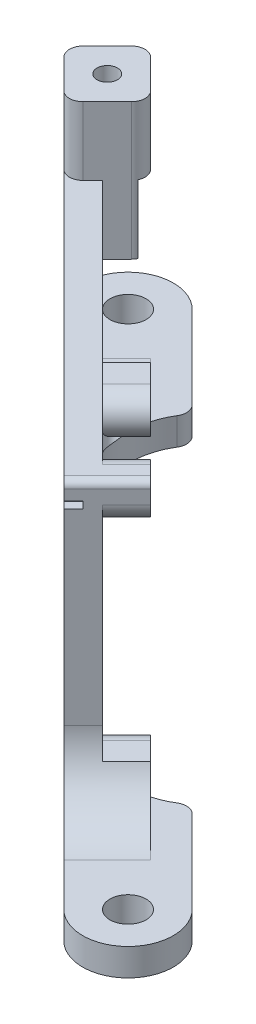
SolidWorks part; units mm, degrees
ref_plane "前视基准面" through (0, 0, 0) normal (0, 0, 1) x (1, 0, 0)
ref_plane "上视基准面" through (0, 0, 0) normal (0, 1, 0) x (1, 0, 0)
ref_plane "右视基准面" through (0, 0, 0) normal (1, 0, 0) x (0, 0, -1)
sketch "草图1" plane through (0, 0, 0) normal (0, 1, 0) x (1, 0, 0)
  line L0 (38.1, -38.1) -> (-38.1, 38.1)
  line L1 (38.1, -38.1) -> (-38.1, 38.1) construction
  line L2 (33.3977, -42.8023) -> (-42.8023, 33.3977)
  line L3 (42.8023, -33.3977) -> (-33.3977, 42.8023)
  circle A0 centre (38.1, -38.1) radius 2.65
  circle A1 centre (-38.1, 38.1) radius 2.65
  arc A2 (33.3977, -42.8023) -> (42.8023, -33.3977) centre (38.1, -38.1) ccw
  arc A3 (-33.3977, 42.8023) -> (-42.8023, 33.3977) centre (-38.1, 38.1) ccw
  point P4 (0, 0)
  point P7 (0, 0)
  dimension "D3" = 5.3
  dimension "D4" = 5.3
  dimension "D5" = 4
  dimension "D1" = 76.2
  dimension "D2" = 76.2
extrude "凸台-拉伸1" add sketch "草图1" along normal blind 4 contours L3 A3 L2 A2 A1 A0 region at (-3.8073, 0, 3.8073)
sketch "草图2" plane through (-4.7023, 0, 4.7023) normal (-0.7071, 0, 0.7071) x (0.7071, 0, 0.7071)
  line L0 (53.8815, 4) -> (-53.8815, 4) construction
  line L1 (35, 45) -> (-35, 45)
  line L2 (35, 45) -> (35, 4)
  line L3 (35, 4) -> (-35, 4)
  line L4 (-35, 45) -> (-35, 4)
  line L5 (35, 45) -> (-35, 4) construction
  line L6 (35, 4) -> (-35, 45) construction
  point P0 (0, 24.5)
  dimension "D1" = 70
  dimension "D2" = 0
  dimension "D3" = 41
extrude "凸台-拉伸2" add sketch "草图2" against normal blind 4
sketch "草图3" plane through (0, 4, 0) normal (0, 1, 0) x (1, 0, 0)
  line L0 (-26.6226, 22.8749) -> (-15.8803, 33.6172)
  line L1 (-15.8803, 33.6172) -> (33.6172, -15.8803)
  line L2 (22.8749, -26.6226) -> (33.6172, -15.8803)
  line M5 (-26.6226, 22.8749) -> (22.8749, -26.6226)
  line M9 (42.8023, -33.3977) -> (-33.3977, 42.8023)
  dimension "D1" = 270
extrude "切除-拉伸1" cut sketch "草图3" against normal blind 4 and the other way through all contours L2 L0 M5 M9 region at (1.4142, 4, -1.4142)
fillet "圆角1" radius 10 2 edges at (22.8749, 2, 26.6226) (-26.6226, 2, -22.8749)
fillet "圆角2" radius 10 2 edges at (21.4607, 4, 28.0368) (-28.0368, 4, -21.4607)
fillet "圆角3" radius 2 2 edges at (22.8836, 4, 26.6312) (-26.6312, 4, -22.8836)
fillet "圆角4" radius 1 2 edges at (21.4607, 45, 28.0368) (-28.0368, 45, -21.4607)
sketch "草图4" plane through (-1.8738, 0, 1.8738) normal (0.7071, 0, -0.7071) x (-0.7071, 0, -0.7071)
  line L0 (0, 45) -> (0, 0)
  line L1 (-34, 45) -> (34, 45) construction
  line L3 (32, 7) -> (-32, 7)
  line L4 (32, 7) -> (32, 42)
  line L5 (32, 42) -> (-32, 42)
  line L6 (-32, 7) -> (-32, 42)
  line L7 (32, 7) -> (-32, 42) construction
  line L8 (32, 42) -> (-32, 7) construction
  circle A0 centre (-32, 42) radius 1.65
  circle A1 centre (-32, 7) radius 1.65
  circle A2 centre (32, 42) radius 1.65
  circle A3 centre (32, 7) radius 1.65
  point P5 (0, 24.5)
  line M7 (-39, 6) -> (-25.0245, 6)
  line M11 (25.0245, 6) -> (39, 6)
  dimension "D4" = 3.3
  dimension "D5" = 3.3
  dimension "D6" = 3.3
  dimension "D7" = 3.3
  dimension "D1" = 20.5
  dimension "D2" = 35
  dimension "D3" = 64
extrude "切除-拉伸2" cut sketch "草图4" against normal mid plane 14 contours L6 A0 L5 | L5 A0 L6 | L4 A2 L5 | L5 A2 L4 | L3 A3 L4 M11 | L4 A3 L3 | L6 A1 L3 M7 | L3 A1 L6 | A3 M11 | A1 M7 region at (-24.6663, 42.2334, -20.9186) region at (-24.0061, 41.2997, -20.2584) region at (20.2584, 41.2997, 24.0061) region at (20.9186, 42.2334, 24.6663) region at (-24.0061, 7.7003, -20.2584) region at (-24.704, 7.0019, -20.9563) region at (20.9563, 7.0019, 24.704) region at (20.2584, 7.7003, 24.0061) region at (-24.5012, 5.735, -20.7536) region at (20.7536, 5.735, 24.5012)
sketch "草图5" plane through (-1.8738, 0, 1.8738) normal (0.7071, 0, -0.7071) x (-0.7071, 0, -0.7071)
  line L1 (32, 4) -> (46.1458, 4)
  line L2 (-32, 42) -> (-35, 42)
  line L3 (-32, 42) -> (-32, 45.9419)
  line L4 (-32, 45.9419) -> (-35, 45.9419)
  line L5 (-35, 42) -> (-35, 45.9419)
  line L6 (32, 42) -> (35, 42)
  line L7 (32, 42) -> (32, 47.5251)
  line L8 (32, 47.5251) -> (35, 47.5251)
  line L9 (35, 42) -> (35, 47.5251)
  line L10 (-32, 7) -> (-39, 7)
  line L11 (-30.6876, 6) -> (-25.0245, 6)
  line L12 (-25.0245, 6) -> (-25.0245, 0)
  line L13 (-25.0245, 0) -> (25.0245, 0)
  line L14 (25.0245, 0) -> (25.0245, 6)
  line L15 (25.0245, 6) -> (30.6876, 6)
  line L16 (33.3124, 6) -> (39, 6)
  line L17 (35, 14) -> (35, 44)
  line L18 (34, 45) -> (-34, 45)
  line L19 (-35, 44) -> (-35, 14)
  line L20 (-39, 6) -> (-33.3124, 6)
  line L21 (-30.6876, 6) -> (-25.0245, 6)
  line L22 (-25.0245, 6) -> (-25.0245, 0)
  line L23 (-25.0245, 0) -> (25.0245, 0)
  line L24 (25.0245, 0) -> (25.0245, 6)
  line L25 (25.0245, 6) -> (30.6876, 6)
  line L26 (33.3124, 6) -> (39, 6)
  line L27 (35, 14) -> (35, 44)
  line L28 (34, 45) -> (-34, 45)
  line L29 (-35, 44) -> (-35, 14)
  line L30 (-39, 6) -> (-33.3124, 6)
  line L31 (-32, 7) -> (-32, 10)
  line L32 (-32, 10) -> (-39, 10)
  line L33 (-39, 7) -> (-39, 10)
  line L34 (32, 7) -> (39.2652, 7)
  line L35 (32, 7) -> (32, 10)
  line L36 (32, 10) -> (39.2652, 10)
  line L37 (39.2652, 7) -> (39.2652, 10)
  line L38 (35, 4) -> (53.8815, 4) construction
  line L39 (46.1458, 4) -> (39.2652, 7)
  line L40 (-32, 4) -> (-46.5387, 4)
  line L41 (-53.8815, 4) -> (-35, 4) construction
  line L42 (-46.5387, 4) -> (-39, 7)
  circle A0 centre (-32, 42) radius 3
  circle A1 centre (-32, 7) radius 3
  circle A2 centre (32, 7) radius 3
  circle A3 centre (32, 42) radius 3
  circle A4 centre (-32, 7) radius 1.65
  circle A5 centre (32, 7) radius 1.65
  arc A6 (39, 6) -> (45, 4) centre (45, 14) ccw construction
  arc A7 (-30.6876, 6) -> (-33.3124, 6) centre (-32, 7) ccw
  arc A8 (33.3124, 6) -> (30.6876, 6) centre (32, 7) ccw
  arc A9 (35, 14) -> (39, 6) centre (45, 14) ccw
  arc A10 (35, 44) -> (34, 45) centre (34, 44) ccw
  arc A11 (-34, 45) -> (-35, 44) centre (-34, 44) ccw
  arc A12 (-39, 6) -> (-35, 14) centre (-45, 14) ccw
  arc A13 (-30.6876, 6) -> (-33.3124, 6) centre (-32, 7) ccw
  arc A14 (33.3124, 6) -> (30.6876, 6) centre (32, 7) ccw
  arc A15 (35, 14) -> (39, 6) centre (45, 14) ccw
  arc A16 (35, 44) -> (34, 45) centre (34, 44) ccw
  arc A17 (-34, 45) -> (-35, 44) centre (-34, 44) ccw
  arc A18 (-39, 6) -> (-35, 14) centre (-45, 14) ccw
  arc A19 (-45, 4) -> (-39, 6) centre (-45, 14) ccw construction
  arc A20 (39, 6) -> (45, 4) centre (45, 14) ccw
  arc A21 (-45, 4) -> (-39, 6) centre (-45, 14) ccw
  arc M1 (-33.3124, 6) -> (-30.6876, 6) centre (-32, 7) cw
  line M2 (-30.6876, 6) -> (-25.0245, 6)
  arc M7 (30.6876, 6) -> (33.3124, 6) centre (32, 7) cw
  line M8 (33.3124, 6) -> (39, 6)
  arc M9 (39, 6) -> (35, 14) centre (45, 14) cw
  line M10 (35, 14) -> (35, 44)
  arc M11 (35, 44) -> (34, 45) centre (34, 44) ccw
  line M12 (34, 45) -> (-34, 45)
  arc M13 (-34, 45) -> (-35, 44) centre (-34, 44) ccw
  line M14 (-35, 44) -> (-35, 14)
  arc M15 (-35, 14) -> (-39, 6) centre (-45, 14) cw
  line M16 (-39, 6) -> (-33.3124, 6)
  circle M17 centre (32, 42) radius 1.65
  circle M18 centre (-32, 42) radius 1.65
  dimension "D1" = 6
  dimension "D3" = 6
  dimension "D4" = 6
  dimension "D5" = 3
  dimension "D6" = 3
  dimension "D2" = 0
extrude "凸台-拉伸3" add sketch "草图5" along normal blind 5 contours L35 A2 L25 M7 | L34 A2 L35 M7 | A2 L34 L36 M9 | A2 L26 L34 M9 | A20 L26 A2 L1 | A5 L25 A2 M8 | A2 L34 M8 M7 | A1 L10 M15 M16 | A21 L40 A1 M16 | A4 L30 A1 M2 | A1 L31 M2 M1 | L31 A1 L10 M1 | A1 L32 L10 M15 | L10 A1 L30 M1 | L2 A0 L3 M18 | L3 A0 L2 M18 | A0 M12 M13 M14 | L6 A3 L7 M17 | L7 A3 L6 M17 | A3 M10 M11 M12 region at (-28.4613, 4.8333, -24.7136) region at (-24.5012, 5.0765, -20.7536) region at (-23.3128, 8.0723, -19.5651) region at (-27.8155, 6.4684, -24.0678) region at (-26.0855, 6.4906, -22.3378) region at (-25.5773, 8.5217, -21.8296) region at (-26.9843, 8.5141, -23.2367) region at (-23.0437, 39.9387, -19.296) region at (-26.1092, 44.2741, -22.3616) region at (-25.5773, 43.5217, -21.8296) region at (20.7536, 5.0765, 24.5012) region at (19.5651, 8.0723, 23.3128) region at (24.7136, 4.8333, 28.4613) region at (19.296, 44.0613, 23.0437) region at (22.3616, 44.2741, 26.1092) region at (21.8296, 43.5217, 25.5773) region at (22.3378, 6.4906, 26.0855) region at (24.0678, 6.4684, 27.8155) region at (23.2367, 8.5141, 26.9843) region at (21.8296, 8.5217, 25.5773)
sketch "草图6" plane through (-4.7023, 0, 4.7023) normal (-0.7071, 0, 0.7071) x (0.7071, 0, 0.7071)
  line L1 (-28.7091, 42) -> (-30.3546, 44.85)
  line L2 (-30.3546, 44.85) -> (-33.6454, 44.85)
  line L3 (-33.6454, 44.85) -> (-35.2909, 42)
  line L4 (-35.2909, 42) -> (-33.6454, 39.15)
  line L5 (-33.6454, 39.15) -> (-30.3546, 39.15)
  line L6 (-30.3546, 39.15) -> (-28.7091, 42)
  line L7 (35.2909, 42) -> (33.6454, 44.85)
  line L8 (33.6454, 44.85) -> (30.3546, 44.85)
  line L9 (30.3546, 44.85) -> (28.7091, 42)
  line L10 (28.7091, 42) -> (30.3546, 39.15)
  line L11 (30.3546, 39.15) -> (33.6454, 39.15)
  line L12 (33.6454, 39.15) -> (35.2909, 42)
  line L13 (35.2909, 7) -> (33.6454, 9.85)
  line L14 (33.6454, 9.85) -> (30.3546, 9.85)
  line L15 (30.3546, 9.85) -> (28.7091, 7)
  line L16 (28.7091, 7) -> (30.3546, 4.15)
  line L17 (30.3546, 4.15) -> (33.6454, 4.15)
  line L18 (33.6454, 4.15) -> (35.2909, 7)
  line L19 (-28.7091, 7) -> (-30.3546, 9.85)
  line L20 (-30.3546, 9.85) -> (-33.6454, 9.85)
  line L21 (-33.6454, 9.85) -> (-35.2909, 7)
  line L22 (-35.2909, 7) -> (-33.6454, 4.15)
  line L23 (-33.6454, 4.15) -> (-30.3546, 4.15)
  line L24 (-30.3546, 4.15) -> (-28.7091, 7)
  circle A0 centre (-32, 42) radius 2.85 construction
  circle A1 centre (32, 42) radius 2.85 construction
  circle A2 centre (32, 7) radius 2.85 construction
  circle A3 centre (-32, 7) radius 2.85 construction
  dimension "D1" = 5.7
  dimension "D2" = 5.7
  dimension "D3" = 5.7
  dimension "D4" = 5.7
extrude "切除-拉伸3" cut sketch "草图6" against normal blind 2
fillet "圆角5" radius 2 2 edges at (-20.0465, 2, -29.451) (29.451, 2, 20.0465)
sketch "草图7" plane through (0, 0, 0) normal (0, 1, 0) x (1, 0, 0)
  circle A0 centre (14.4684, -760.0717) radius 5
  circle A1 centre (-14.7658, -793.7018) radius 5
  dimension "D1" = 10
  dimension "D2" = 10
sketch "草图8" plane through (0, 0, 0) normal (0, 1, 0) x (1, 0, 0)
  circle A0 centre (14.4684, -23.7283) radius 5
  circle A1 centre (-14.7658, 9.9018) radius 5
  dimension "D1" = 10
  dimension "D2" = 10
extrude "切除-拉伸5" cut sketch "草图8" along normal blind 5
sketch "草图9" plane through (0, 45, 0) normal (0, 1, 0) x (1, 0, 0)
  line L0 (-18.8444, 15.0967) -> (-15.3089, 18.6323)
  line L1 (20.7536, -24.5012) -> (-24.5012, 20.7536) construction
  line L2 (-18.8444, 15.0967) -> (-24.5012, 20.7536)
  line L3 (-24.5012, 20.7536) -> (-20.9657, 24.2891)
  line L4 (-20.9657, 24.2891) -> (-15.3089, 18.6323)
  line L5 (-26.6226, 22.8749) -> (-29.451, 20.0465) construction
  line L6 (-18.8444, 22.1678) -> (-22.3799, 18.6323)
  line L7 (-18.8444, 22.1678) -> (-11.7733, 15.0967)
  line L8 (-22.3799, 18.6323) -> (-15.3089, 11.5612)
  line L9 (-11.7733, 15.0967) -> (-15.3089, 11.5612)
  line L10 (-18.8444, 22.1678) -> (-15.3089, 11.5612) construction
  line L11 (-22.3799, 18.6323) -> (-11.7733, 15.0967) construction
  line L12 (19.3394, -28.7439) -> (-28.7439, 19.3394) construction
  circle A1 centre (-18.4908, 15.4503) radius 1.5
  line M7 (20.7536, -24.5012) -> (-24.5012, 20.7536)
  line M8 (-24.5012, 20.7536) -> (-20.9657, 24.2891)
  dimension "D4" = 4.5
  dimension "D5" = 3
  dimension "D1" = 11
  dimension "D2" = 16
  dimension "D3" = 5
extrude "凸台-拉伸4" add sketch "草图9" against normal blind 10 contours A1 L9 L7 L0 M7 | A1 L0 L4 L6 L8 | L6 L4 L2 M8 region at (-18.861, 45, -18.9043) region at (-15.0369, 45, -15.0801) region at (-21.6728, 45, -21.4607)
sketch "草图10" plane through (0, 45, 0) normal (0, 1, 0) x (1, 0, 0)
  line L0 (-11.7733, 15.0967) -> (-18.1373, 8.7328)
  line L1 (19.3394, -28.7439) -> (-28.7439, 19.3394) construction
  line L2 (-18.1373, 8.7328) -> (-25.2084, 15.8038)
  line L3 (-25.2084, 15.8038) -> (-18.8444, 22.1678)
  line L4 (-22.3799, 25.7033) -> (-11.7733, 15.0967) construction
  line L5 (-18.8444, 22.1678) -> (-11.7733, 15.0967)
  line L6 (-17.8444, 14.0967) -> (-19.8444, 16.0967) construction
  line L7 (-17.8444, 14.0967) -> (-19.8444, 16.0967)
  arc A0 (-17.8444, 14.0967) -> (-19.8444, 16.0967) centre (-18.4908, 15.4503) ccw construction
  arc A1 (-17.8444, 14.0967) -> (-19.8444, 16.0967) centre (-18.4908, 15.4503) ccw
  dimension "D1" = 5
extrude "凸台-拉伸5" add sketch "草图10" along normal blind 10
fillet "圆角6" radius 2 4 edges at (-11.7733, 45, -15.0967) (-18.1373, 50, -8.7328) (-25.2084, 50, -15.8038) (-18.8444, 50, -22.1678)
sketch "草图11" plane through (1.6617, 0, -1.6617) normal (0.7071, 0, -0.7071) x (-0.7071, 0, -0.7071)
  line L0 (32, 40.35) -> (32, 43.65) construction
  circle A0 centre (32, 42) radius 1.65
extrude "切除-拉伸6" cut sketch "草图11" against normal blind 10
sketch "草图12" plane through (0, 55, 0) normal (0, 1, 0) x (1, 0, 0)
  circle A0 centre (-18.4908, 15.4503) radius 1.5
extrude "切除-拉伸7" cut sketch "草图12" against normal offset from surface (17 mm away) 3 up to face at (-17.5485, 35, -16.915)
sketch "草图13" plane through (0, 35, 0) normal (0, -1, 0) x (1, 0, 0)
  circle A0 centre (-18.4908, -15.4503) radius 1.5
extrude "凸台-拉伸6" add sketch "草图13" against normal blind 3
sketch "草图14" plane through (1.6617, 0, -1.6617) normal (0.7071, 0, -0.7071) x (-0.7071, 0, -0.7071)
  line L0 (29, 42) -> (29, 45)
  line L1 (29, 45) -> (19, 45)
  line L2 (19, 45) -> (19, 35)
  line L3 (19, 35) -> (32, 35)
  line L4 (32, 35) -> (32, 39)
  circle A0 centre (32, 42) radius 3
  arc A1 (32, 39) -> (35, 42) centre (32, 42) ccw construction
  line M3 (21, 55) -> (21, 35)
  line M4 (21, 35) -> (32, 35)
  line M5 (32, 35) -> (32, 39)
  line M9 (34, 45) -> (27, 45)
  dimension "D1" = 0
extrude "切除-拉伸8" cut sketch "草图14" against normal blind 1.3 contours A0 L0 L1 M9 M3 M4 M5 | L2 L3 L1 M3 region at (-16.5807, 39.61, -19.9041) region at (-12.4804, 40, -15.8038)
